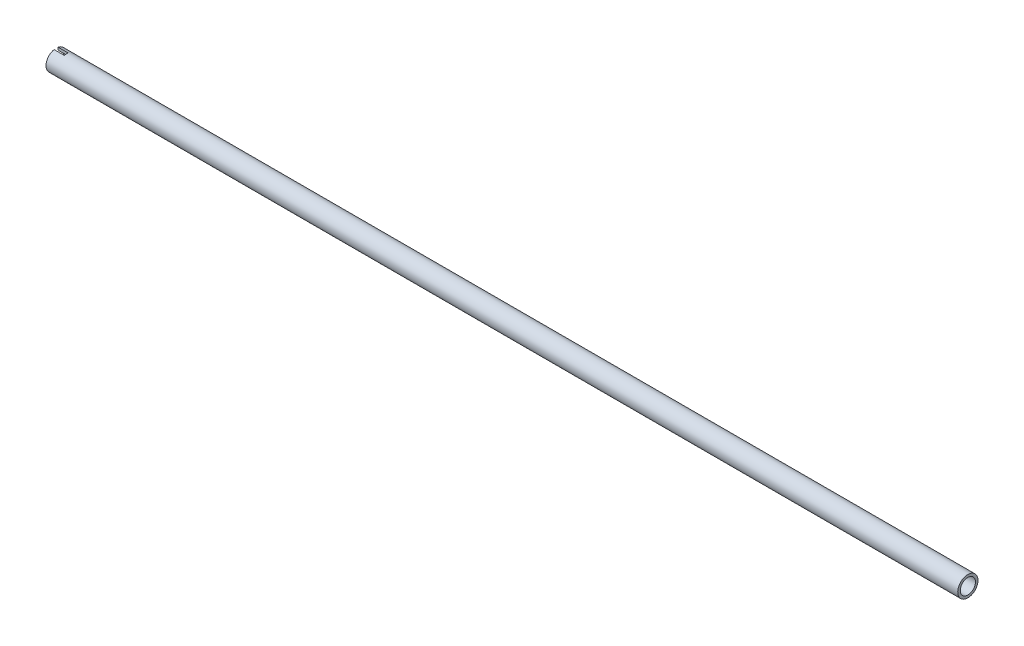
SolidWorks part; units mm, degrees
ref_plane "Front Plane" through (0, 0, 0) normal (0, 0, 1) x (1, 0, 0)
ref_plane "Top Plane" through (0, 0, 0) normal (0, 1, 0) x (1, 0, 0)
ref_plane "Right Plane" through (0, 0, 0) normal (1, 0, 0) x (0, 0, -1)
ref_axis "Axis1" through (-88.99, 0, 0) along (1, 0, 0)
sketch "Sketch1" plane through (0, 0, 0) normal (1, 0, 0) x (0, 0, -1)
  circle A0 centre (0, 0) radius 0.75
  circle A1 centre (0, 0) radius 1
  dimension "D1" = 1.5
  dimension "D2" = 2
extrude "Boss-Extrude1" add sketch "Sketch1" along normal blind 90
sketch "Sketch2" plane through (0, 0, 0) normal (-1, 0, 0) x (0, 0, 1)
  line L0 (0, 0) -> (0, 0.6106) construction
  line L2 (-0.2, 0.6106) -> (-0.2, 1.0992)
  line L3 (-0.2, 1.0992) -> (0.2, 1.0992)
  line L4 (0.2, 1.0992) -> (0.2, 0.6106)
  arc A0 (-0.2, 0.6106) -> (0.2, 0.6106) centre (0, 0.6106) ccw
  dimension "D1" = 0.4
extrude "Cut-Extrude1" cut sketch "Sketch2" against normal blind 1
